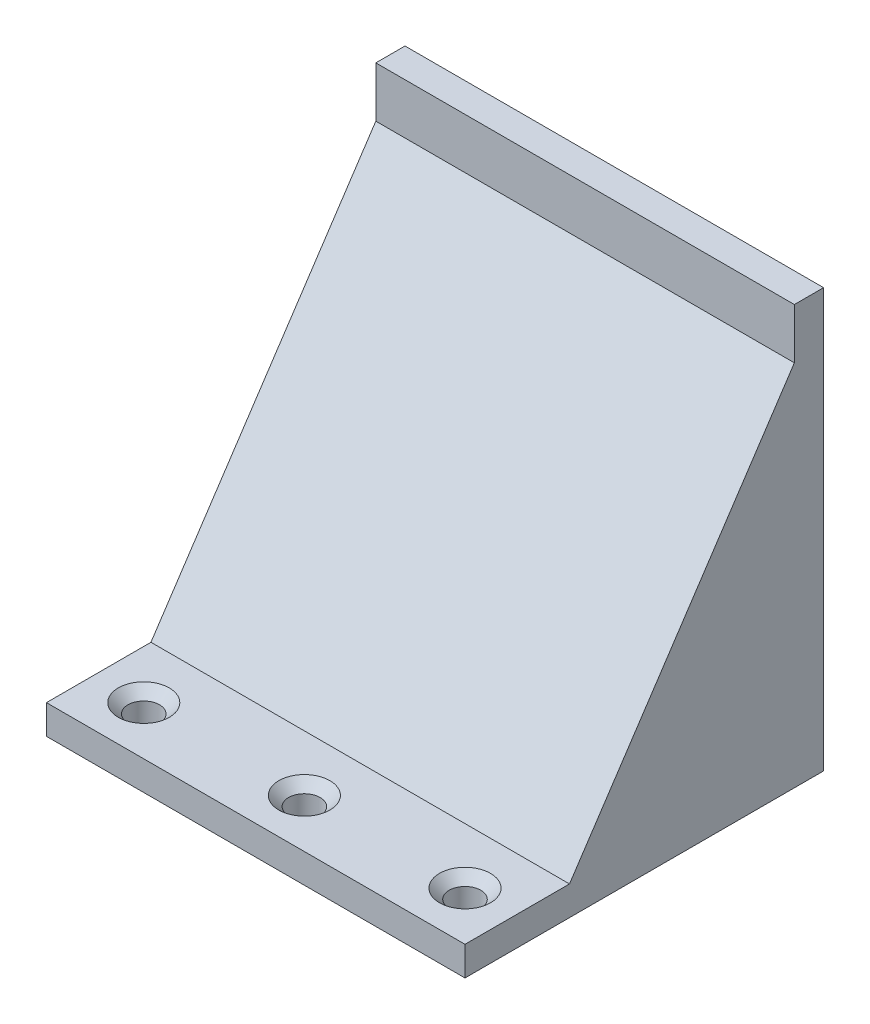
SolidWorks part; units mm, degrees
ref_plane "Piano frontale" through (0, 0, 0) normal (0, 0, 1) x (1, 0, 0)
ref_plane "Piano superiore" through (0, 0, 0) normal (0, 1, 0) x (1, 0, 0)
ref_plane "Piano destro" through (0, 0, 0) normal (1, 0, 0) x (0, 0, -1)
sketch "Schizzo1" plane through (0, 0, 0) normal (0, 0, 1) x (1, 0, 0)
  line L1 (-21.5, 21.5) -> (21.5, 21.5)
  line L2 (-21.5, 21.5) -> (-21.5, -21.5)
  line L3 (-21.5, -21.5) -> (21.5, -21.5)
  line L4 (21.5, 21.5) -> (21.5, -21.5)
  line L5 (-21.5, 21.5) -> (21.5, -21.5) construction
  line L6 (-21.5, -21.5) -> (21.5, 21.5) construction
  point P0 (0, 0)
  dimension "D1" = 43
  dimension "D2" = 43
extrude "Estrusione-Estrusione1" add sketch "Schizzo1" along normal blind 3
sketch "Schizzo2" plane through (-21.5, 0, 0) normal (-1, 0, 0) x (0, 0, 1)
  line L0 (26.1004, -18.5) -> (3, 16.3134)
  line L1 (3, 16.3134) -> (3, -21.5)
  line L2 (3, -21.5) -> (36.837, -21.5)
  line L4 (36.837, -21.5) -> (36.837, -18.5)
  line L5 (3, 21.5) -> (3, -21.5) construction
  line L7 (26.1004, -18.5) -> (36.837, -18.5)
extrude "Estrusione-Estrusione2" add sketch "Schizzo2" against normal blind 43
sketch "Schizzo3" plane through (0, -18.5, 0) normal (0, 1, 0) x (1, 0, 0)
  line L0 (21.5, -36.837) -> (21.5, -26.1004) construction
  line L1 (21.5, -36.837) -> (-21.5, -36.837) construction
  circle A0 centre (0, -31.837) radius 1.62
  circle A1 centre (16.5, -31.837) radius 1.62
  circle A2 centre (-16.5, -31.837) radius 1.62
  point P4 (21.5, -31.4687)
  dimension "D3" = 3.24
  dimension "D1" = 5
  dimension "D2" = 5
  dimension "D4" = 3
extrude "Taglio-Estrusione1" cut sketch "Schizzo3" against normal blind 43 contours A1
chamfer "Smusso1" distance 1 angle 45 1 edges at (14.88, -18.5, 31.837)
extrude "Taglio-Estrusione2" cut sketch "Schizzo3<3>" against normal blind 43 contours A0
sketch "Schizzo3<3>" plane through (0, -18.5, 0) normal (0, 1, 0) x (1, 0, 0) same geometry as "Schizzo3"
extrude "Taglio-Estrusione3" cut sketch "Schizzo3<4>" against normal blind 43 contours A2
sketch "Schizzo3<4>" plane through (0, -18.5, 0) normal (0, 1, 0) x (1, 0, 0) same geometry as "Schizzo3"
chamfer "Smusso2" distance 1 angle 45 1 edges at (-1.62, -18.5, 31.837)
chamfer "Smusso3" distance 1 angle 45 1 edges at (-18.12, -18.5, 31.837)
